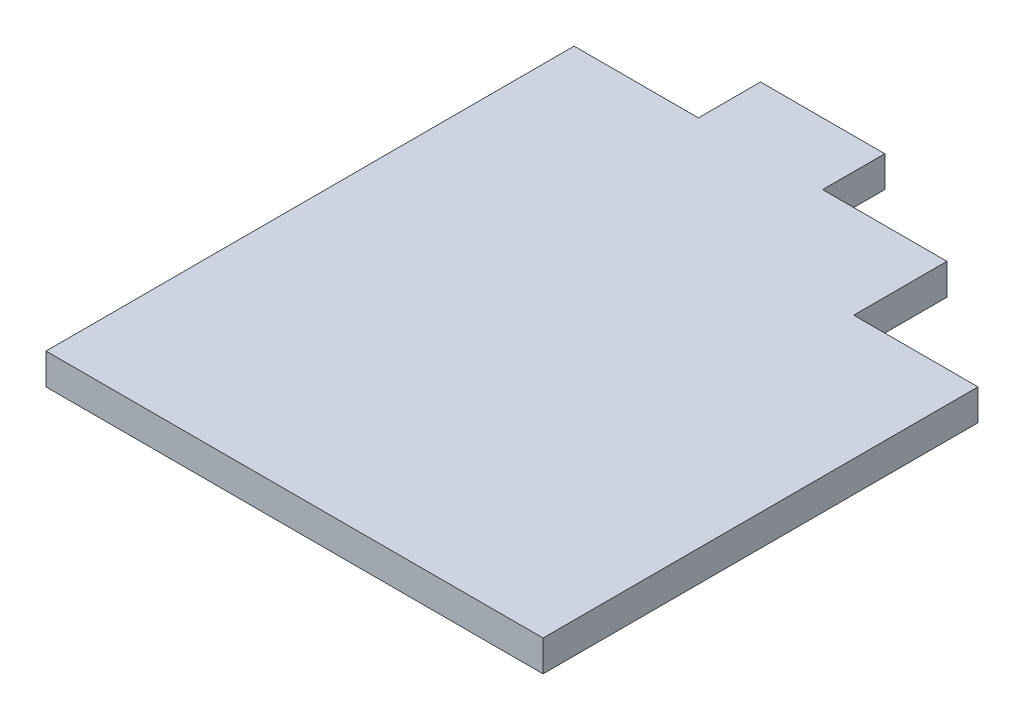
SolidWorks part; units mm, degrees
ref_plane "Front Plane" through (0, 0, 0) normal (0, 0, 1) x (1, 0, 0)
ref_plane "Top Plane" through (0, 0, 0) normal (0, 1, 0) x (1, 0, 0)
ref_plane "Right Plane" through (0, 0, 0) normal (1, 0, 0) x (0, 0, -1)
sketch "Sketch1" plane through (0, 0, 0) normal (0, 1, 0) x (1, 0, 0)
  line L1 (0, 0) -> (80, 0)
  line L2 (0, 0) -> (0, 85)
  line L3 (20, 95) -> (40, 95)
  line L4 (80, 0) -> (80, 70)
  line L7 (0, 85) -> (20, 85)
  line L8 (20, 95) -> (20, 85)
  line L10 (40, 95) -> (40, 85)
  line L14 (60, 85) -> (60, 70)
  line L15 (60, 70) -> (80, 70)
  line L17 (40, 85) -> (60, 85)
  dimension "D2" = 95
  dimension "D3" = 10
  dimension "D4" = 15
  dimension "D5" = 20
extrude "Boss-Extrude1" add sketch "Sketch1" along normal blind 5
